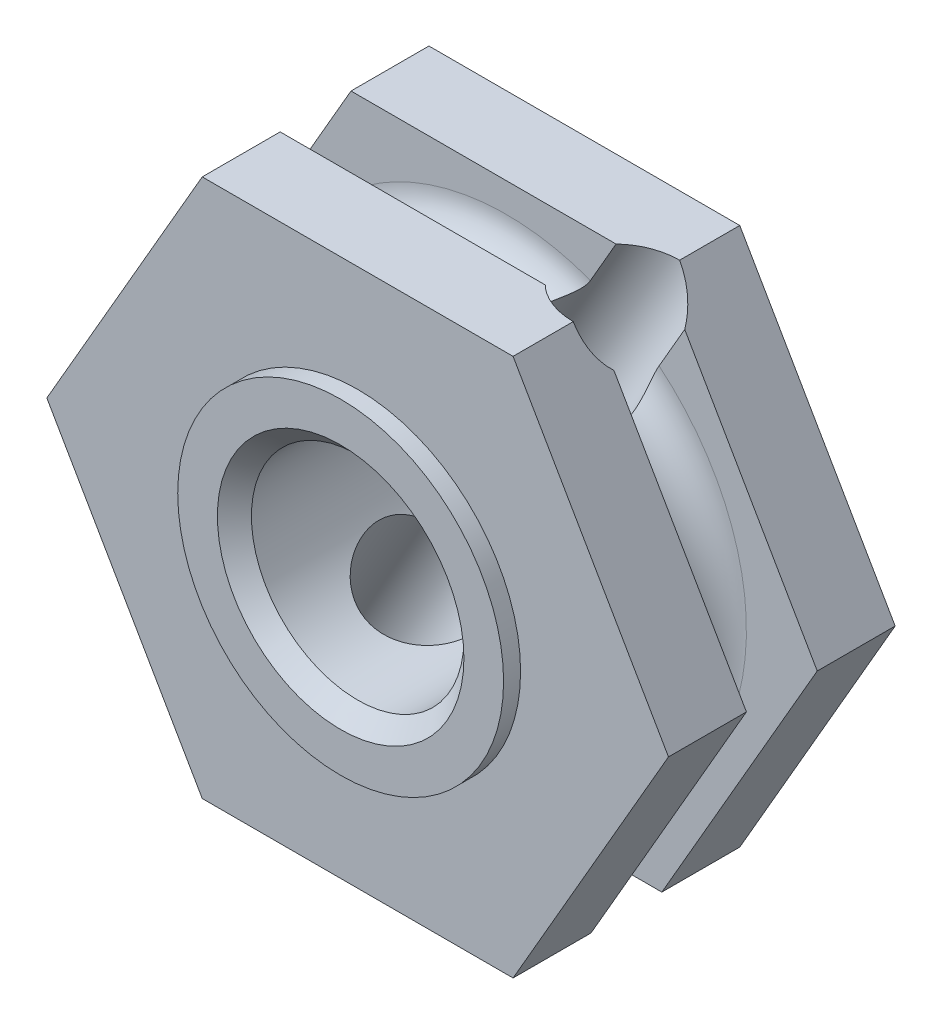
SolidWorks part; units mm, degrees
ref_plane "Front Plane" through (0, 0, 0) normal (0, 0, 1) x (1, 0, 0)
ref_plane "Top Plane" through (0, 0, 0) normal (0, 1, 0) x (1, 0, 0)
ref_plane "Right Plane" through (0, 0, 0) normal (1, 0, 0) x (0, 0, -1)
sketch "Sketch1" plane through (0, 0, 0) normal (0, 0, 1) x (1, 0, 0)
  line L1 (3.4829, 6.0325) -> (-3.4829, 6.0325)
  line L2 (-3.4829, 6.0325) -> (-6.9657, 0)
  line L3 (-6.9657, 0) -> (-3.4829, -6.0325)
  line L4 (-3.4829, -6.0325) -> (3.4829, -6.0325)
  line L5 (3.4829, -6.0325) -> (6.9657, 0)
  line L6 (6.9657, 0) -> (3.4829, 6.0325)
  circle A0 centre (0, 0) radius 6.0325 construction
  dimension "D1" = 12.065
extrude "Boss-Extrude1" add sketch "Sketch1" along normal mid plane 5.08
sketch "Sketch2" plane through (0, 0, 2.54) normal (0, 0, 1) x (1, 0, 0)
  circle A0 centre (0, 0) radius 2.3813
  circle A1 centre (0, 0) radius 3.6513
  dimension "D1" = 4.7625
  dimension "D2" = 1.27
extrude "Boss-Extrude2" add sketch "Sketch2" along normal blind 0.381
sketch "Sketch3" plane through (0, 0, 2.54) normal (0, 0, 1) x (1, 0, 0)
  circle A0 centre (0, 0) radius 2.3813 construction
  circle A1 centre (0, 0) radius 2.3813
extrude "Cut-Extrude1" cut sketch "Sketch3" against normal through all
chamfer "Chamfer1" distance 0.381 1 edges at (2.3813, 0, 2.921)
ref_plane "Plane1" through (3.4829, 6.0325, 0) normal (-0.5, -0.866, 0) x (0, 0, -1)
sketch "Sketch4" plane through (3.4829, 6.0325, 0) normal (-0.5, -0.866, 0) x (0, 0, -1)
  line L0 (-2.54, 0) -> (2.54, 0) construction
  circle A0 centre (0, 0) radius 1.1913
  dimension "D1" = 2.3825
extrude "Cut-Extrude2" cut sketch "Sketch4" along normal through all
ref_plane "Plane2" through (0, 0, 0) normal (-0.866, 0.5, 0) x (0, 0, 1)
sketch "Sketch5" plane through (0, 0, 0) normal (-0.866, 0.5, 0) x (0, 0, 1)
  line L0 (1.1913, -6.9657) -> (1.1913, -2.3813)
  line L1 (-1.1913, -2.3813) -> (-1.1913, -6.9657)
  line L2 (1.1913, 2.3813) -> (1.1913, 6.9657)
  line L3 (-1.1913, 6.9657) -> (-1.1913, 2.3813)
  line L4 (2.54, -2.3813) -> (2.921, -2.7623)
  line L5 (2.921, 2.7623) -> (2.54, 2.3813)
  line L6 (2.921, 3.6513) -> (2.54, 3.6513)
  line L7 (2.54, -3.6513) -> (2.921, -3.6513)
  line L8 (2.921, 3.6513) -> (2.921, 2.7623)
  line L9 (2.921, -2.7623) -> (2.921, -3.6513)
  line L10 (-2.54, 6.9657) -> (-2.54, 2.3813)
  line L11 (-2.54, -2.3813) -> (-2.54, -6.9657)
  line L12 (2.54, 6.9657) -> (2.54, 3.6513)
  line L13 (2.54, -3.6513) -> (2.54, -6.9657)
  line L14 (-1.1913, -6.9657) -> (-2.54, -6.9657)
  line L15 (2.54, -6.9657) -> (1.1913, -6.9657)
  line L16 (2.54, 2.3813) -> (1.1913, 2.3813)
  line L17 (-1.1913, 2.3813) -> (-2.54, 2.3813)
  line L18 (-2.54, -2.3813) -> (-1.1913, -2.3813)
  line L19 (1.1913, -2.3813) -> (2.54, -2.3813)
  line L20 (2.54, 6.9657) -> (1.1913, 6.9657)
  line L21 (-1.1913, 6.9657) -> (-2.54, 6.9657)
  line L22 (-1.1913, 6.9657) -> (-2.54, 6.9657) construction
  line L23 (2.54, 6.9657) -> (1.1913, 6.9657) construction
  line L24 (1.1913, -2.3813) -> (2.54, -2.3813) construction
  line L25 (-2.54, -2.3813) -> (-1.1913, -2.3813) construction
  line L26 (-1.1913, 2.3813) -> (-2.54, 2.3813) construction
  line L27 (2.54, 2.3813) -> (1.1913, 2.3813) construction
  line L28 (2.54, -6.9657) -> (1.1913, -6.9657) construction
  line L29 (-1.1913, -6.9657) -> (-2.54, -6.9657) construction
  line L30 (2.54, -3.6513) -> (2.54, -6.9657) construction
  line L31 (2.54, 6.9657) -> (2.54, 3.6513) construction
  line L32 (-2.54, -2.3813) -> (-2.54, -6.9657) construction
  line L33 (-2.54, 6.9657) -> (-2.54, 2.3813) construction
  line L34 (2.921, -2.7623) -> (2.921, -3.6513) construction
  line L35 (2.921, 3.6513) -> (2.921, 2.7623) construction
  line L36 (2.54, -3.6513) -> (2.921, -3.6513) construction
  line L37 (2.921, 3.6513) -> (2.54, 3.6513) construction
  line L38 (2.921, 2.7623) -> (2.54, 2.3813) construction
  line L39 (2.54, -2.3813) -> (2.921, -2.7623) construction
  line L40 (-1.1913, 6.9657) -> (-1.1913, 2.3813) construction
  line L41 (1.1913, 2.3813) -> (1.1913, 6.9657) construction
  line L42 (-1.1913, -2.3813) -> (-1.1913, -6.9657) construction
  line L43 (1.1913, -6.9657) -> (1.1913, -2.3813) construction
  line L44 (-0.7938, 6.9657) -> (-0.7938, 5.3782)
  line L45 (0.7937, 5.3782) -> (0.7937, 6.9657)
  line L46 (0.7937, 6.9657) -> (-0.7938, 6.9657)
  line L47 (-1000.0889, 0) -> (48999.9111, 0) construction
  arc A0 (-0.7938, 5.3782) -> (0.7937, 5.3782) centre (0, 5.3782) ccw
  dimension "D1" = 0.7937
  dimension "D2" = 1.5875
revolve "Cut-Revolve1" cut sketch "Sketch5" angle 360 about L47
